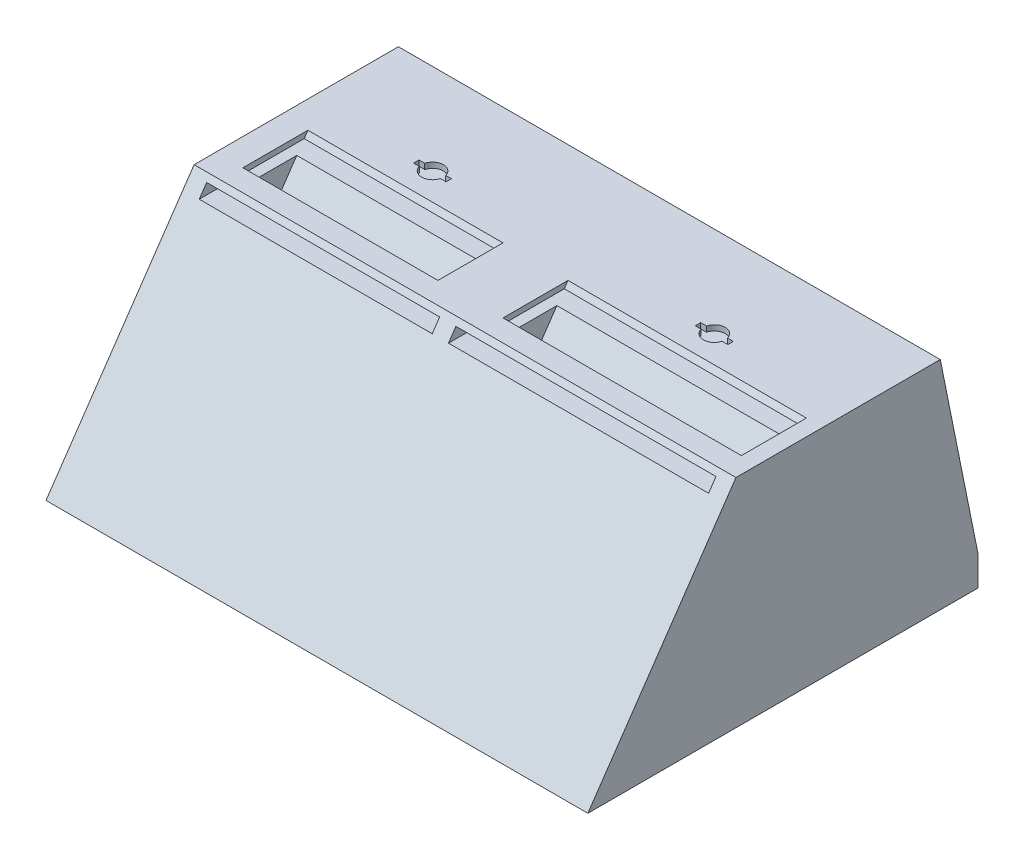
SolidWorks part; units mm, degrees
ref_plane "Ebene vorne" through (0, 0, 0) normal (0, 0, 1) x (1, 0, 0)
ref_plane "Ebene oben" through (0, 0, 0) normal (0, 1, 0) x (1, 0, 0)
ref_plane "Ebene rechts" through (0, 0, 0) normal (1, 0, 0) x (0, 0, -1)
sketch "Skizze1" plane through (0, 0, 0) normal (0, 0, 1) x (1, 0, 0)
  line L1 (-25, -15) -> (25, -15)
  line L2 (-25, -15) -> (-25, 15)
  line L3 (-25, 15) -> (25, 15)
  line L4 (25, -15) -> (25, 15)
  line L5 (-25, -15) -> (25, 15) construction
  line L6 (-25, 15) -> (25, -15) construction
  point P0 (0, 0)
  dimension "D1" = 50
  dimension "D2" = 30
extrude "Aufsatz-Linear austragen1" add sketch "Skizze1" along normal blind 40
ref_plane "Ebene1" through (0, 0, 0) normal (-1, 0, 0) x (0, 0, 1)
sketch "Skizze2" plane through (0, 0, 0) normal (-1, 0, 0) x (0, 0, 1)
  line L0 (7.5, 15) -> (28, -15)
  line L1 (40, 15) -> (0, 15) construction
  line L2 (40, -15) -> (0, -15) construction
  line L3 (28, -15) -> (34, -15)
  line L4 (34, -15) -> (13.5, 15)
  line L5 (13.5, 15) -> (7.5, 15)
  line L6 (40, 15) -> (40, -15) construction
  line L8 (26.6333, -13) -> (32.6333, -13)
  dimension "D1" = 6
  dimension "D2" = 6
  dimension "D3" = 7.5
  dimension "D4" = 2
extrude "FPV_Sender" cut sketch "Skizze2" against normal blind 22 from offset 1.5 contours L0 L8 L4 L5 region at (0, 1, 20.0667) offset against normal yes
sketch "Skizze4" plane through (0, 0, 0) normal (-1, 0, 0) x (0, 0, 1)
  line L0 (13.5, 15) -> (7.5, 15)
  line L1 (7.5, 15) -> (26.6333, -13)
  line L2 (7.5, 15) -> (26.6333, -13) construction
  line L3 (26.6333, -13) -> (32.6333, -13)
  line L4 (32.6333, -13) -> (13.5, 15) construction
  line L5 (32.6333, -13) -> (13.5, 15)
  dimension "D1" = 28
extrude "Empfänger" cut sketch "Skizze4" along normal blind 18 from offset 4.5
sketch "Skizze5" plane through (-25, 0, 0) normal (-1, 0, 0) x (0, 0, 1)
  line L0 (15.5, 15) -> (40, 15)
  line L1 (40, 15) -> (0, 15) construction
  line L2 (40, 15) -> (40, -20.8537)
  line L3 (40, 15) -> (40, -15) construction
  line L4 (40, -20.8537) -> (15.5, 15)
  line L5 (32.6333, -13) -> (13.5, 15) construction
  line L6 (5.5, 15) -> (0, -12.25)
  line L7 (0, 15) -> (0, -15) construction
  line L8 (0, -12.25) -> (0, 15)
  line L9 (0, 15) -> (5.5, 15)
  line L10 (40, -15) -> (0, -15) construction
  dimension "D1" = 2
  dimension "D2" = 2.75
  dimension "D3" = 2
extrude "Schnitt-Linear austragen3" cut sketch "Skizze5" against normal through all and the other way through all
sketch "Skizze7" plane through (25, 0, 0) normal (1, 0, 0) x (0, 0, -1)
  line L0 (-5.5, 15) -> (-15.5, 15)
  line L1 (-15.5, 15) -> (-22.3333, 5)
  line L2 (-15.5, 15) -> (-36, -15) construction
  line L3 (-22.3333, 5) -> (-3.4817, 5)
  line L4 (0, -12.25) -> (-5.5, 15) construction
  line L5 (-3.4817, 5) -> (-5.5, 15)
  dimension "D1" = 10
extrude "Schnitt-Linear austragen5" cut sketch "Skizze7" against normal up to surface (50 mm away) up to face at (-25, 0.55, 11.95)
shell "Wandung2" thickness 2 removed face at (0, -15, 18)
sketch "Skizze6" plane through (0, -13, 0) normal (0, 1, 0) x (1, 0, 0)
  line L0 (23.5, -26.6333) -> (1.5, -26.6333) construction
  line L1 (1.5, -32.6333) -> (8.5, -32.6333)
  line L2 (1.5, -32.6333) -> (1.5, -26.6333)
  line L3 (1.5, -26.6333) -> (8.5, -26.6333)
  line L4 (8.5, -32.6333) -> (8.5, -26.6333)
  dimension "D1" = 7
extrude "Schnitt-Linear austragen4" cut sketch "Skizze6" against normal up to surface (2 mm away) up to face at (0, -15, 18)
sketch "Skizze8" plane through (0, -13, 0) normal (0, 1, 0) x (1, 0, 0)
  line L0 (-22.5, -26.6333) -> (-4.5, -26.6333) construction
  line L1 (-4.5, -32.6333) -> (-8.5, -32.6333)
  line L2 (-4.5, -32.6333) -> (-4.5, -26.6333)
  line L3 (-4.5, -26.6333) -> (-8.5, -26.6333)
  line L4 (-8.5, -32.6333) -> (-8.5, -26.6333)
  dimension "D1" = 4
extrude "Schnitt-Linear austragen7" cut sketch "Skizze8" against normal up to surface (2 mm away) up to face at (5, -15, 29.6333)
sketch "Skizze9" plane through (-25, 0, 0) normal (-1, 0, 0) x (0, 0, 1)
  line L0 (22.675, 4.5) -> (7.675, 4.5)
  line L1 (22.3333, 5) -> (36, -15) construction
  line L2 (7.675, 4.5) -> (7.675, 3.5)
  line L3 (7.675, 3.5) -> (23.3583, 3.5)
  line L4 (23.3583, 3.5) -> (22.675, 4.5)
  line L5 (22.3333, 5) -> (3.4817, 5) construction
  dimension "D1" = 15
  dimension "D2" = 0.5
  dimension "D3" = 1
extrude "Schnitt-Linear austragen8" cut sketch "Skizze9" against normal blind 21.5 from offset 1.5 offset against normal yes
sketch "Skizze10" plane through (25, 0, 0) normal (1, 0, 0) x (0, 0, -1)
  line L0 (-22.675, 4.5) -> (-7.675, 4.5)
  line L2 (-22.675, 4.5) -> (-7.675, 4.5) construction
  line L3 (-7.675, 4.5) -> (-7.675, 3.5)
  line L4 (-7.675, 3.5) -> (-23.3583, 3.5) construction
  line L5 (-7.675, 3.5) -> (-23.3583, 3.5)
  line L6 (-23.3583, 3.5) -> (-22.675, 4.5)
  dimension "D1" = 15
extrude "Schnitt-Linear austragen9" cut sketch "Skizze10" against normal blind 24 from offset 1.5 offset against normal yes
sketch "Skizze11" plane through (0, 5, 0) normal (0, 1, 0) x (1, 0, 0)
  line L1 (14, -11.5833) -> (11, -11.5833)
  line L2 (14, -11.5833) -> (14, -12.0833)
  line L3 (14, -12.0833) -> (11, -12.0833)
  line L4 (11, -11.5833) -> (11, -12.0833)
  line L5 (14, -11.5833) -> (11, -12.0833) construction
  line L6 (14, -12.0833) -> (11, -11.5833) construction
  line L7 (23.5, -14.3333) -> (23.5, -20.3333) construction
  line L8 (23.5, -14.3333) -> (1.5, -14.3333) construction
  line L10 (-12, -12.0833) -> (-15, -12.0833)
  line L11 (-12, -12.0833) -> (-12, -11.5833)
  line L12 (-12, -11.5833) -> (-15, -11.5833)
  line L13 (-15, -12.0833) -> (-15, -11.5833)
  line L14 (-12, -12.0833) -> (-15, -11.5833) construction
  line L15 (-12, -11.5833) -> (-15, -12.0833) construction
  line L16 (-22.5, -14.3333) -> (-22.5, -20.3333) construction
  line L17 (-22.5, -14.3333) -> (-4.5, -14.3333) construction
  circle A0 centre (12.5, -11.8333) radius 1
  circle A1 centre (-13.5, -11.8333) radius 1
  dimension "D1" = 11
  dimension "D4" = 2
  dimension "D6" = 9
  dimension "D7" = 2
  dimension "D2" = 2.5
  dimension "D3" = 3
  dimension "D5" = 0.5
  dimension "D8" = 0.5
  dimension "D9" = 3
  dimension "D10" = 2.5
extrude "Schnitt-Linear austragen10" cut sketch "Skizze11" against normal up to surface (2 mm away) contours L10 A1 | A1 L12 L13 L10 | L10 A1 L12 | L12 A1 | A1 L10 L11 L12 | A0 L3 L2 L1 | L3 A0 | L1 A0 | L1 L4 L3 L2 region at (13.7447, 5, 11.8333) region at (12.5, 5, 11.271) region at (12.5, 5, 12.3957) region at (-12.2553, 5, 11.8333) region at (-13.5, 5, 12.3957) region at (-13.5, 5, 11.8333) region at (-14.7447, 5, 11.8333) region at (-13.5, 5, 11.271) up to face at (-0.75, 3, 13.2378)
